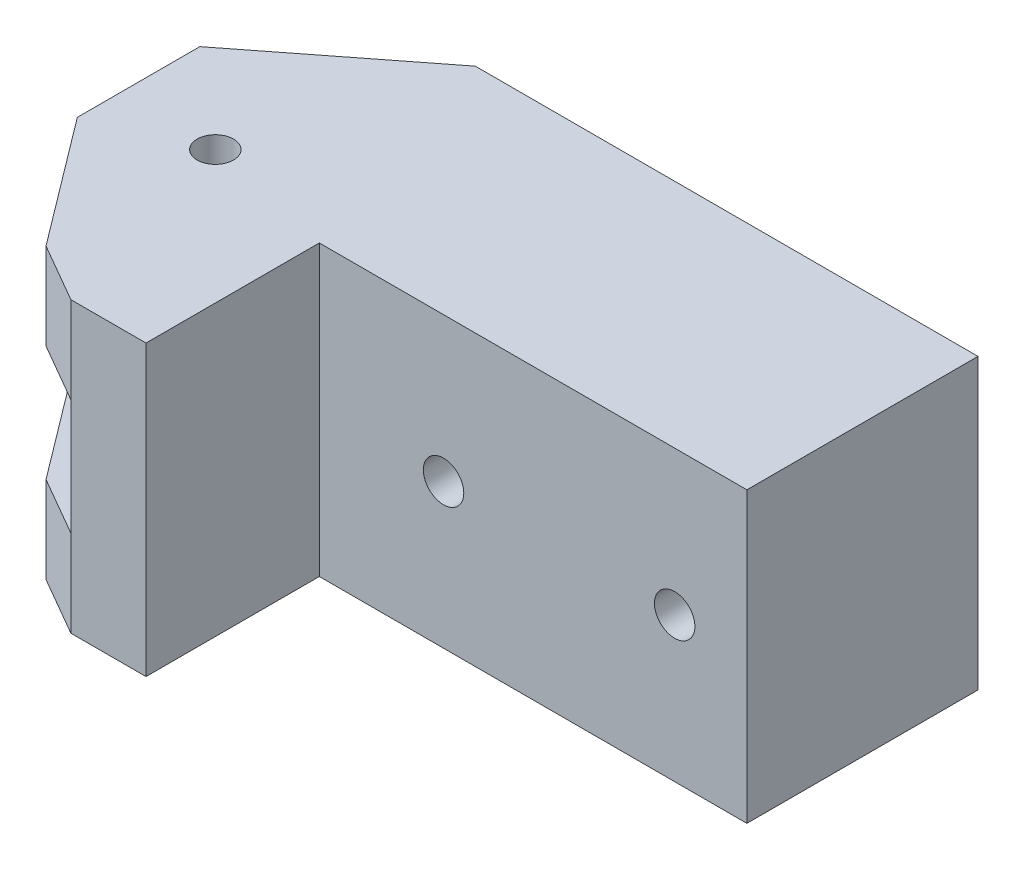
SolidWorks part; units mm, degrees
ref_plane "Front Plane" through (0, 0, 0) normal (0, 0, 1) x (1, 0, 0)
ref_plane "Top Plane" through (0, 0, 0) normal (0, 1, 0) x (1, 0, 0)
ref_plane "Right Plane" through (0, 0, 0) normal (1, 0, 0) x (0, 0, -1)
sketch "Sketch1" plane through (0, 0, 0) normal (0, 1, 0) x (1, 0, 0)
  line L0 (0, 0) -> (-43.5, 0)
  line L1 (-43.5, 0) -> (-43.5, -35) construction
  line L2 (-43.5, -35) -> (-37, -35)
  line L3 (-37, -35) -> (-37, -20)
  line L4 (-37, -20) -> (0, -20)
  line L5 (0, -20) -> (0, 0)
  line L6 (-43.5, 0) -> (-56.8853, -10.4577)
  line L7 (-56.8853, -10.4577) -> (-56.8853, -21.0577)
  line L8 (-56.8853, -21.0577) -> (-48.5962, -32.0577)
  line L9 (-48.5962, -32.0577) -> (-43.5, -35)
  line L10 (-43.5, -17.5) -> (-48.5, -17.5) construction
  circle A0 centre (-48.5, -17.5) radius 1.575
  point P14 (0, 0)
  dimension "D11" = 3.15
  dimension "D1" = 43.5
  dimension "D2" = 35
  dimension "D3" = 20
  dimension "D4" = 37
  dimension "D5" = 30
  dimension "D6" = 38
  dimension "D7" = 10.6
  dimension "D8" = 37
  dimension "D9" = 11
  dimension "D10" = 5
extrude "Boss-Extrude1" add sketch "Sketch1" along normal mid plane 25
sketch "Sketch2" plane through (0, 0, 35) normal (0, 0, 1) x (1, 0, 0)
  line L0 (-43.5, 12.5) -> (-43.5, -12.5) construction
  line L1 (-43.5, -5) -> (-56.8853, -5)
  line L2 (-43.5, -5) -> (-43.5, 5)
  line L3 (-43.5, 5) -> (-56.8853, 5)
  line L4 (-56.8853, -5) -> (-56.8853, 5)
  line L5 (-56.8853, 12.5) -> (-56.8853, -12.5) construction
  line L6 (-56.8853, 12.5) -> (-48.5962, 12.5) construction
  dimension "D1" = 7.5
  dimension "D2" = 10
extrude "Cut-Extrude1" cut sketch "Sketch2" against normal through all
sketch "Sketch3" plane through (0, 0, 20) normal (0, 0, 1) x (1, 0, 0)
  line L0 (0, 12.5) -> (0, -12.5) construction
  line L1 (0, 0) -> (-26.25, 0) construction
  circle A0 centre (-26.25, 0) radius 1.75
  circle A1 centre (-6.25, 0) radius 1.75
  point P7 (0, 0)
  dimension "D1" = 3.5
  dimension "D2" = 26.25
  dimension "D3" = 6.25
extrude "Cut-Extrude2" cut sketch "Sketch3" against normal blind 25
